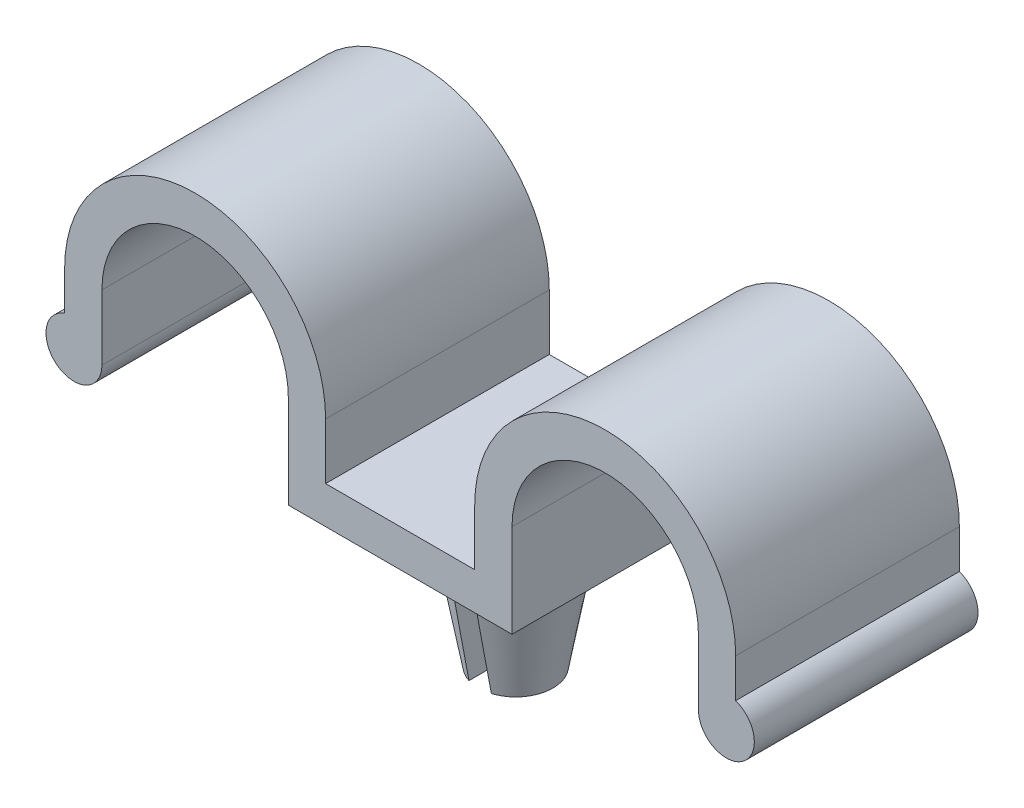
SolidWorks part; units mm, degrees
ref_plane "Front" through (0, 0, 0) normal (0, 0, 1) x (1, 0, 0)
ref_plane "Top" through (0, 0, 0) normal (0, 1, 0) x (1, 0, 0)
ref_plane "Right" through (0, 0, 0) normal (1, 0, 0) x (0, 0, -1)
sketch "Sketch1" plane through (0, 0, 0) normal (0, 0, 1) x (1, 0, 0)
  line L0 (-9.525, -1.905) -> (-4.445, -1.905)
  line L1 (4.445, 0) -> (4.445, -1.3245)
  line L2 (3.175, 0) -> (3.175, -2.2225)
  line L3 (-3.175, 0) -> (-3.175, -3.175)
  line L4 (-4.445, 0) -> (-4.445, -1.905)
  line L5 (-6.985, -2.2225) -> (-6.985, 0.9964) construction
  line L6 (-3.175, -3.175) -> (-10.795, -3.175)
  line L8 (-9.525, 0) -> (-9.525, -1.905)
  line L9 (-10.795, 0) -> (-10.795, -3.175)
  line L10 (-17.145, 0) -> (-17.145, -2.2225)
  line L11 (-18.415, 0) -> (-18.415, -1.3245)
  arc A0 (3.175, 0) -> (-3.175, 0) centre (0, 0) ccw
  arc A1 (4.445, 0) -> (-4.445, 0) centre (0, 0) ccw
  arc A2 (3.175, -2.2225) -> (4.445, -1.3245) centre (4.1275, -2.2225) ccw
  arc A3 (-17.145, -2.2225) -> (-18.415, -1.3245) centre (-18.0975, -2.2225) cw
  arc A4 (-18.415, 0) -> (-9.525, 0) centre (-13.97, 0) cw
  arc A5 (-17.145, 0) -> (-10.795, 0) centre (-13.97, 0) cw
  dimension "D1" = 6.35
  dimension "D2" = 4.445
  dimension "D4" = 1.27
  dimension "D5" = 1.905
  dimension "D6" = 6.985
  dimension "D3" = 3.175
extrude "Base-Extrude" add sketch "Sketch1" along normal mid plane 7.62
sketch "Sketch4" plane through (0, 0, 0) normal (0, 0, 1) x (1, 0, 0)
  line L0 (-6.858, -3.175) -> (-6.858, -7.874)
  line L2 (-6.858, -7.874) -> (-5.588, -7.874)
  line L3 (-6.858, -3.175) -> (-6.858, -0.7652) construction
  line L4 (-5.08, -4.826) -> (-5.334, -4.826)
  line L5 (-5.334, -4.826) -> (-5.334, -3.175)
  line L6 (-5.334, -3.175) -> (-6.858, -3.175)
  line L7 (-5.08, -4.826) -> (-5.08, -5.08)
  line L8 (-5.08, -5.08) -> (-5.588, -7.874)
  line L9 (-10.795, -3.175) -> (-3.175, -3.175) construction
  dimension "D1" = 6.858
  dimension "D2" = 1.524
  dimension "D3" = 1.651
  dimension "D4" = 3.048
  dimension "D5" = 1.27
  dimension "D6" = 0.254
  dimension "D7" = 1.778
revolve "Boss-Revolve1" add sketch "Sketch4" angle 360 about L3
sketch "Sketch5" plane through (0, 0, 0) normal (0, 0, 1) x (1, 0, 0)
  line L0 (-8.128, -7.874) -> (-5.588, -7.874) construction
  line L1 (-7.239, -7.874) -> (-6.477, -7.874)
  line L2 (-7.239, -7.874) -> (-7.239, -3.81)
  line L4 (-6.477, -7.874) -> (-6.477, -3.81)
  arc A0 (-6.477, -3.81) -> (-7.239, -3.81) centre (-6.858, -3.81) ccw
  dimension "D1" = 0.762
  dimension "D2" = 6.858
  dimension "D3" = 4.064
extrude "Cut-Extrude1" cut sketch "Sketch5" against normal through all and the other way through all
sketch "Sketch6" plane through (0, 0, 3.81) normal (0, 0, 1) x (1, 0, 0)
  point P0 (0, 0)
  point P1 (-13.97, 0)
sketch "Sketch7" plane through (0, 0, -3.81) normal (0, 0, -1) x (-1, 0, 0)
  point P0 (0, 0)
  point P1 (13.97, 0)
ref_axis "Clip Axis" through (0, 0, 3.81) along (0, 0, -1)
ref_axis "Clip Axis2" through (-13.97, 0, 3.81) along (0, 0, -1)
ref_axis "Axis of Rotation" through (-6.858, -3.175, 0) along (0, -1, 0)
other "RPoint1"
other "RPoint2"
other "RPoint3"
other "RPoint4"
